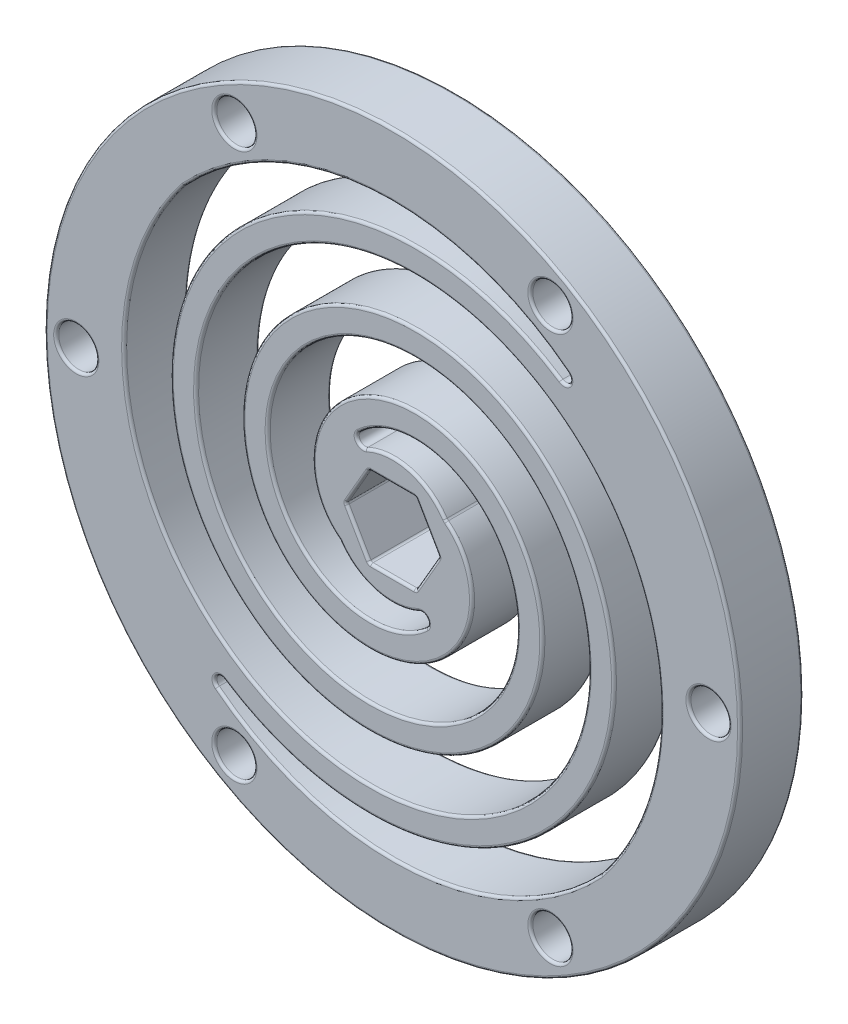
SolidWorks part; units mm, degrees
ref_plane "Front Plane" through (0, 0, 0) normal (0, 0, 1) x (1, 0, 0)
ref_plane "Top Plane" through (0, 0, 0) normal (0, 1, 0) x (1, 0, 0)
ref_plane "Right Plane" through (0, 0, 0) normal (1, 0, 0) x (0, 0, -1)
sketch "Sketch2" plane through (0, 0, 0) normal (0, 0, 1) x (1, 0, 0)
  line L0 (0, 0) -> (27.5, 0) construction
  line L1 (3.6662, 0) -> (1.8331, 3.175)
  line L2 (1.8331, 3.175) -> (-1.8331, 3.175)
  line L3 (-1.8331, 3.175) -> (-3.6662, 0)
  line L4 (-3.6662, 0) -> (-1.8331, -3.175)
  line L5 (-1.8331, -3.175) -> (1.8331, -3.175)
  line L6 (1.8331, -3.175) -> (3.6662, 0)
  line L7 (0, 0) -> (3.6662, 0) construction
  circle A0 centre (0, 0) radius 27.5
  circle A1 centre (0, 0) radius 22.5
  circle A2 centre (0, 0) radius 25 construction
  circle A3 centre (-25, 0) radius 1.5875
  circle A4 centre (0, 0) radius 5
  circle A5 centre (-12.5, 21.6506) radius 1.5875
  circle A6 centre (12.5, 21.6506) radius 1.5875
  circle A7 centre (25, 0) radius 1.5875
  circle A8 centre (12.5, -21.6506) radius 1.5875
  circle A9 centre (-12.5, -21.6506) radius 1.5875
  circle A10 centre (0, 0) radius 3.175 construction
  point P20 (0, 0)
  dimension "D1" = 50
  dimension "D2" = 55
  dimension "D3" = 45
  dimension "D4" = 3.175
  dimension "D5" = 10
  dimension "D7" = 6.35
  dimension "D8" = 0
  dimension "D6" = 6
sketch "Sketch3" plane through (0, 0, 0) normal (0, 0, 1) x (1, 0, 0)
  circle A0 centre (0, 0) radius 5
  circle A1 centre (0, 0) radius 5 construction
curve "Helix/Spiral1"
sketch "Sketch4" plane through (0, 0, 0) normal (0, 0, 1) x (1, 0, 0)
  line L1 (3.6662, 0) -> (1.8331, 3.175)
  line L2 (1.8331, 3.175) -> (-1.8331, 3.175)
  line L3 (-1.8331, 3.175) -> (-3.6662, 0)
  line L4 (-3.6662, 0) -> (-1.8331, -3.175)
  line L5 (-1.8331, -3.175) -> (1.8331, -3.175)
  line L6 (1.8331, -3.175) -> (3.6662, 0)
  circle A0 centre (0, 0) radius 27.5
  circle A1 centre (0, 0) radius 27.5 construction
  arc A2 (21.0974, 7.8198) -> (16.4884, -15.3096) centre (0, 0) ccw
  circle A3 centre (0, 0) radius 22.5 construction
  arc A4 (-4.1867, -2.7335) -> (-4.1828, 2.7394) centre (0, 0) ccw
  circle A5 centre (0, 0) radius 5 construction
  circle A6 centre (0, 0) radius 3.175 construction
  circle A7 centre (-25, 0) radius 1.5875
  circle A8 centre (-25, 0) radius 1.5875 construction
  circle A9 centre (-12.5, 21.6506) radius 1.5875
  circle A10 centre (12.5, 21.6506) radius 1.5875
  circle A11 centre (25, 0) radius 1.5875
  circle A12 centre (12.5, -21.6506) radius 1.5875
  circle A13 centre (-12.5, -21.6506) radius 1.5875
  spline S2 degree 3 poles (-921.9687, 1775.2435) (120.6606, -2.4111) (-4.8813, -17.0729) (-4.2797, 2.414) (-4.1558, 3.0013) (-3.6679, 4.1424) (-3.3002, 4.7041) (-2.3359, 5.6942) (-1.7333, 6.1283) (-0.3515, 6.7692) (0.4351, 6.979) (2.0951, 7.1004) (2.9764, 7.0121) (4.709, 6.5027) (5.5675, 6.0792) (7.1263, 4.9117) (7.8323, 4.163) (8.9643, 2.407) (9.394, 1.3934) (9.878, -0.7846) (9.9334, -1.956) (9.6158, -4.3077) (9.2415, -5.4949) (8.0664, -7.7186) (7.262, -8.761) (5.2882, -10.5401) (4.1135, -11.2809) (1.5171, -12.3274) (0.089, -12.6353) (-2.8511, -12.7334) (-4.3697, -12.5234) (-7.3011, -11.5652) (-8.72, -10.8146) (-11.2595, -8.8244) (-12.3849, -7.5806) (-14.1678, -4.7221) (-14.8283, -3.1019) (-15.559, 0.3326) (-15.6302, 2.1531) (-15.1274, 5.7722) (-14.552, 7.577) (-12.7805, 10.9347) (-11.581, 12.4931) (-8.6672, 15.1438) (-6.9482, 16.24) (-3.1749, 17.7964) (-1.1149, 18.2587) (3.1053, 18.4467) (5.2715, 18.1723) (9.4409, 16.8734) (11.4497, 15.8467) (15.0444, 13.1234) (16.6348, 11.4229) (19.1699, 7.5217) (20.1175, 5.3159) (21.2117, 0.6472) (21.3593, -1.8216) (20.7894, -6.7266) (20.0707, -9.1687) (17.8084, -13.7181) (16.2618, -15.8304) (12.4887, -19.443) (10.2578, -20.9468) (-48.904, -47.2318) (-226.7337, 148.1709) (1422.9512, 1363.8577) knots -1.044974 -1.044974 -1.044974 -1.044974 0.03125 0.03125 0.0625 0.0625 0.09375 0.09375 0.125 0.125 0.15625 0.15625 0.1875 0.1875 0.21875 0.21875 0.25 0.25 0.28125 0.28125 0.3125 0.3125 0.34375 0.34375 0.375 0.375 0.40625 0.40625 0.4375 0.4375 0.46875 0.46875 0.5 0.5 0.53125 0.53125 0.5625 0.5625 0.59375 0.59375 0.625 0.625 0.65625 0.65625 0.6875 0.6875 0.71875 0.71875 0.75 0.75 0.78125 0.78125 0.8125 0.8125 0.84375 0.84375 0.875 0.875 0.90625 0.90625 0.9375 0.9375 0.96875 0.96875 1.691459 1.691459 1.691459 1.691459 only from (-4.0603, 0.3419) to (-0.0726, -24.0026)
  spline S3 degree 3 poles (-4.1828, 2.7394) (-4.1195, 3.0167) (-4.0297, 3.2962) (-3.6679, 4.1424) (-3.3002, 4.7041) (-2.3359, 5.6942) (-1.7333, 6.1283) (-0.3515, 6.7692) (0.4351, 6.979) (2.0951, 7.1004) (2.9764, 7.0121) (4.709, 6.5027) (5.5675, 6.0792) (7.1263, 4.9117) (7.8323, 4.163) (8.9643, 2.407) (9.394, 1.3934) (9.878, -0.7846) (9.9334, -1.956) (9.6158, -4.3077) (9.2415, -5.4949) (8.0664, -7.7186) (7.262, -8.761) (5.2882, -10.5401) (4.1135, -11.2809) (1.5171, -12.3274) (0.089, -12.6353) (-2.8511, -12.7334) (-4.3697, -12.5234) (-7.3011, -11.5652) (-8.72, -10.8146) (-11.2595, -8.8244) (-12.3849, -7.5806) (-14.1678, -4.7221) (-14.8283, -3.1019) (-15.559, 0.3326) (-15.6302, 2.1531) (-15.1274, 5.7722) (-14.552, 7.577) (-12.7805, 10.9347) (-11.581, 12.4931) (-8.6672, 15.1438) (-6.9482, 16.24) (-3.1749, 17.7964) (-1.1149, 18.2587) (3.1053, 18.4467) (5.2715, 18.1723) (9.4409, 16.8734) (11.4497, 15.8467) (15.0444, 13.1234) (16.6348, 11.4229) (19.1699, 7.5217) (20.1175, 5.3159) (21.2117, 0.6472) (21.3593, -1.8216) (20.7894, -6.7266) (20.0707, -9.1687) (18.2649, -12.8) (17.4425, -14.0989) (16.4884, -15.3096) knots 0.047404 0.047404 0.047404 0.047404 0.0625 0.0625 0.09375 0.09375 0.125 0.125 0.15625 0.15625 0.1875 0.1875 0.21875 0.21875 0.25 0.25 0.28125 0.28125 0.3125 0.3125 0.34375 0.34375 0.375 0.375 0.40625 0.40625 0.4375 0.4375 0.46875 0.46875 0.5 0.5 0.53125 0.53125 0.5625 0.5625 0.59375 0.59375 0.625 0.625 0.65625 0.65625 0.6875 0.6875 0.71875 0.71875 0.75 0.75 0.78125 0.78125 0.8125 0.8125 0.84375 0.84375 0.875 0.875 0.90625 0.90625 0.924888 0.924888 0.924888 0.924888
  spline S4 degree 3 poles (-701.7537, 1870.0142) (184.6387, -12.0204) (-7.1764, -26.603) (-6.2709, 2.7296) (-6.093, 3.5576) (-5.4086, 5.1586) (-4.9053, 5.9226) (-3.5964, 7.2666) (-2.7968, 7.8397) (-0.9711, 8.6865) (0.0471, 8.956) (2.1915, 9.1128) (3.3089, 8.9989) (5.5046, 8.3535) (6.5743, 7.8239) (8.5175, 6.3686) (9.3837, 5.4476) (10.7748, 3.2897) (11.2948, 2.0598) (11.882, -0.5833) (11.9472, -1.9883) (11.566, -4.8107) (11.1205, -6.2199) (9.724, -8.8624) (8.7766, -10.0884) (6.4517, -12.1839) (5.08, -13.0477) (2.0459, -14.2706) (0.391, -14.6263) (-3.0198, -14.7401) (-4.7676, -14.4975) (-8.146, -13.3932) (-9.7689, -12.5337) (-12.678, -10.2537) (-13.9577, -8.838) (-15.9889, -5.5815) (-16.7357, -3.7473) (-17.564, 0.1456) (-17.6434, 2.1964) (-17.0761, 6.2794) (-16.4301, 8.3033) (-14.4402, 12.0749) (-13.0998, 13.8152) (-9.8402, 16.7805) (-7.9268, 17.9998) (-3.7216, 19.7344) (-1.4371, 20.2463) (3.2495, 20.4551) (5.6436, 20.1512) (10.2586, 18.7135) (12.4715, 17.5817) (16.438, 14.5767) (18.1847, 12.7081) (20.9739, 8.416) (22.0116, 5.9992) (23.2122, 0.8767) (23.3729, -1.8211) (22.7491, -7.1889) (21.9652, -9.8507) (19.4955, -14.8171) (17.8131, -17.1141) (13.7037, -21.0486) (11.2825, -22.6801) (-52.776, -51.1406) (-239.5534, 161.1192) (1378.94, 1402.9741) knots -1.077999 -1.077999 -1.077999 -1.077999 0.03125 0.03125 0.0625 0.0625 0.09375 0.09375 0.125 0.125 0.15625 0.15625 0.1875 0.1875 0.21875 0.21875 0.25 0.25 0.28125 0.28125 0.3125 0.3125 0.34375 0.34375 0.375 0.375 0.40625 0.40625 0.4375 0.4375 0.46875 0.46875 0.5 0.5 0.53125 0.53125 0.5625 0.5625 0.59375 0.59375 0.625 0.625 0.65625 0.65625 0.6875 0.6875 0.71875 0.71875 0.75 0.75 0.78125 0.78125 0.8125 0.8125 0.84375 0.84375 0.875 0.875 0.90625 0.90625 0.9375 0.9375 0.96875 0.96875 1.688715 1.688715 1.688715 1.688715 only from (-5.9397, -0.3419) to (0.0726, -25.9974)
  spline S5 degree 3 poles (-4.1867, -2.7335) (-5.5181, -1.7681) (-6.3558, -0.0215) (-6.2709, 2.7296) (-6.093, 3.5576) (-5.4086, 5.1586) (-4.9053, 5.9226) (-3.5964, 7.2666) (-2.7968, 7.8397) (-0.9711, 8.6865) (0.0471, 8.956) (2.1915, 9.1128) (3.3089, 8.9989) (5.5046, 8.3535) (6.5743, 7.8239) (8.5175, 6.3686) (9.3837, 5.4476) (10.7748, 3.2897) (11.2948, 2.0598) (11.882, -0.5833) (11.9472, -1.9883) (11.566, -4.8107) (11.1205, -6.2199) (9.724, -8.8624) (8.7766, -10.0884) (6.4517, -12.1839) (5.08, -13.0477) (2.0459, -14.2706) (0.391, -14.6263) (-3.0198, -14.7401) (-4.7676, -14.4975) (-8.146, -13.3932) (-9.7689, -12.5337) (-12.678, -10.2537) (-13.9577, -8.838) (-15.9889, -5.5815) (-16.7357, -3.7473) (-17.564, 0.1456) (-17.6434, 2.1964) (-17.0761, 6.2794) (-16.4301, 8.3033) (-14.4402, 12.0749) (-13.0998, 13.8152) (-9.8402, 16.7805) (-7.9268, 17.9998) (-3.7216, 19.7344) (-1.4371, 20.2463) (3.2495, 20.4551) (5.6436, 20.1512) (10.2586, 18.7135) (12.4715, 17.5817) (16.438, 14.5767) (18.1847, 12.7081) (20.1461, 9.6899) (20.654, 8.7729) (21.0974, 7.8198) knots -0.044468 -0.044468 -0.044468 -0.044468 0.03125 0.03125 0.0625 0.0625 0.09375 0.09375 0.125 0.125 0.15625 0.15625 0.1875 0.1875 0.21875 0.21875 0.25 0.25 0.28125 0.28125 0.3125 0.3125 0.34375 0.34375 0.375 0.375 0.40625 0.40625 0.4375 0.4375 0.46875 0.46875 0.5 0.5 0.53125 0.53125 0.5625 0.5625 0.59375 0.59375 0.625 0.625 0.65625 0.65625 0.6875 0.6875 0.71875 0.71875 0.75 0.75 0.78125 0.78125 0.8125 0.8125 0.825201 0.825201 0.825201 0.825201
  point P37 (0, 0)
  dimension "D2" = 1
  dimension "D3" = 1
  dimension "D1" = 6
extrude "Boss-Extrude1" add sketch "Sketch4" along normal blind 5
pattern_circular "CirPattern1" count 2 over 360 about axis through (0, 0, 5) along (0, 0, -1) of "Boss-Extrude1"
fillet "Fillet1" radius 0.5 6 edges
fillet "Fillet2" radius 0.2 56 edges at (1.8331, 3.175, 2.5) (3.6662, 0, 2.5) (-3.6662, 0, 2.5) (-1.8331, 3.175, 2.5) (1.8331, -3.175, 2.5) (-1.8331, -3.175, 2.5) (-10.9125, -21.6506, 0) (14.0875, -21.6506, 0) (26.5875, 0, 0) (14.0875, 21.6506, 0) (-10.9125, 21.6506, 0) (-23.4125, 0, 0) (27.5, 0, 0) (0, -3.175, 0) (-2.7496, -1.5875, 0) (-2.7496, 1.5875, 0) (0, 3.175, 0) (2.7496, 1.5875, 0) (2.7496, -1.5875, 0) (-10.9125, -21.6506, 5) (26.5875, 0, 5) (-10.9125, 21.6506, 5) (27.5, 0, 5) (-23.4125, 0, 5) (14.0875, 21.6506, 5) (14.0875, -21.6506, 5) (0, 3.175, 5) (-2.7496, 1.5875, 5) (-2.7496, -1.5875, 5) (0, -3.175, 5) (2.7496, -1.5875, 5) (2.7496, 1.5875, 5)
equation "\"t\"= 2mm"
equation "\"b\"= 5mm"
equation "\"rev\"= 1.75"
equation "\"Spring ID\"= 10mm"
equation "\"Bolt Circle Diameter\"= 50mm"
equation "\"D5@Sketch2\"=\"Spring ID\""
equation "\"D1@Sketch2\"=\"Bolt Circle Diameter\""
equation "\"D2@Sketch2\"=\"Bolt Circle Diameter\" + 5"
equation "\"D3@Sketch2\"=\"Bolt Circle Diameter\" - 5"
equation "\"D5@Helix/Spiral1\"=\"rev\""
equation "\"Pitch\"= ( \"Bolt Circle Diameter\" - \"Spring ID\" ) / ( 2 * \"rev\" )"
equation "\"D2@Sketch4\"=\"t\"/2"
equation "\"D3@Sketch4\"=\"t\"/2"
equation "\"D1@Boss-Extrude1\"=\"b\""
equation "\"D4@Helix/Spiral1\"=\"Pitch\""
